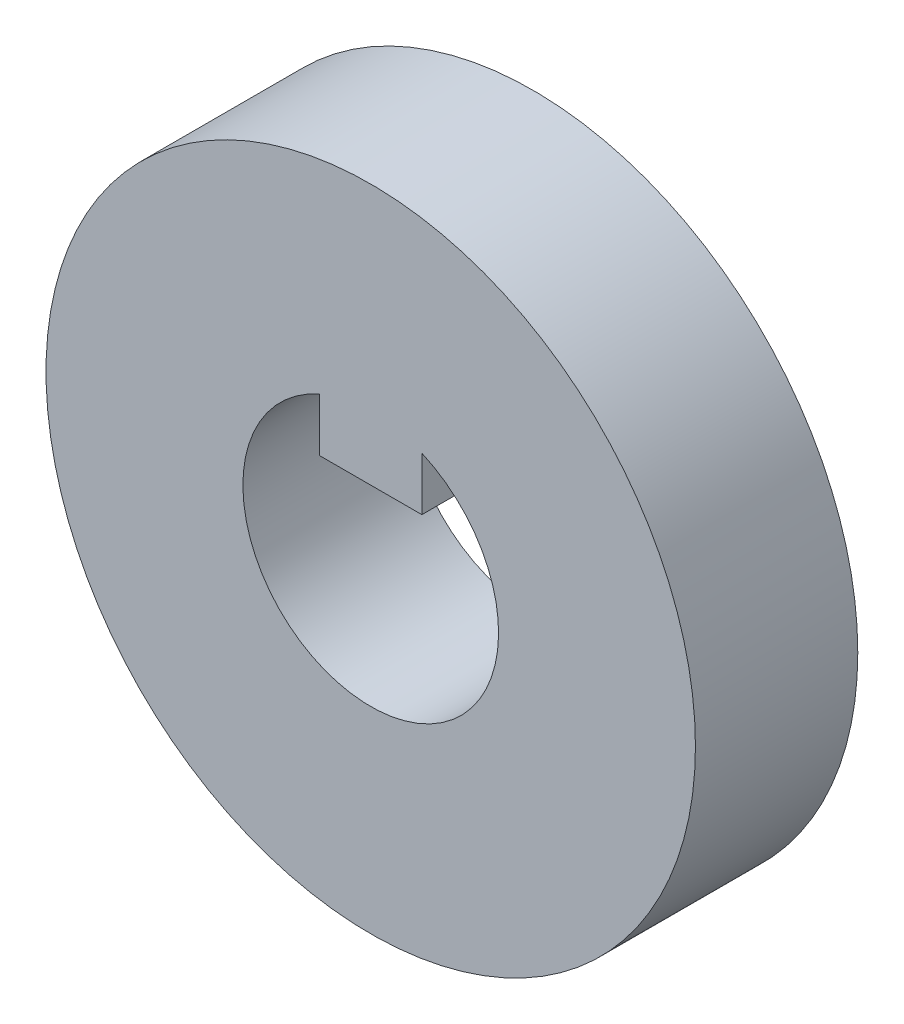
SolidWorks part; units mm, degrees
ref_plane "Front Plane" through (0, 0, 0) normal (0, 0, 1) x (1, 0, 0)
ref_plane "Top Plane" through (0, 0, 0) normal (0, 1, 0) x (1, 0, 0)
ref_plane "Right Plane" through (0, 0, 0) normal (1, 0, 0) x (0, 0, -1)
sketch "Sketch1" plane through (0, 0, 0) normal (0, 0, 1) x (1, 0, 0)
  line L1 (4, 15) -> (-4, 15)
  line L2 (4, 15) -> (4, 5)
  line L3 (4, 5) -> (-4, 5)
  line L4 (-4, 15) -> (-4, 5)
  line L5 (4, 15) -> (-4, 5) construction
  line L6 (4, 5) -> (-4, 15) construction
  circle A0 centre (0, 0) radius 25.4
  circle A1 centre (0, 0) radius 10
  point P4 (0, 10)
  dimension "D1" = 50.8
  dimension "D2" = 20
  dimension "D3" = 8
  dimension "D4" = 10
extrude "Boss-Extrude1" add sketch "Sketch1" along normal blind 12.7 contours A0 A1 L4 L1 L2 | L2 L1 L4 L3 region at (-24.6816, 0, 0)
equation "\"shaftDiam\" = 20mm"
equation "\"keyW\" = 8mm"
equation "\"keyL\" = 10mm"
equation "\"clearance\" = .8mm"
equation "\"shafDiam_\"= \"shaftDiam\""
equation "\"keyL_\"= \"keyL\""
equation "\"keyW_\"= \"keyW\""
equation "\"D3@Sketch1\"=\"keyW_\""
equation "\"D4@Sketch1\"=\"keyL_\""
equation "\"D2@Sketch1\"=\"shafDiam_\""
